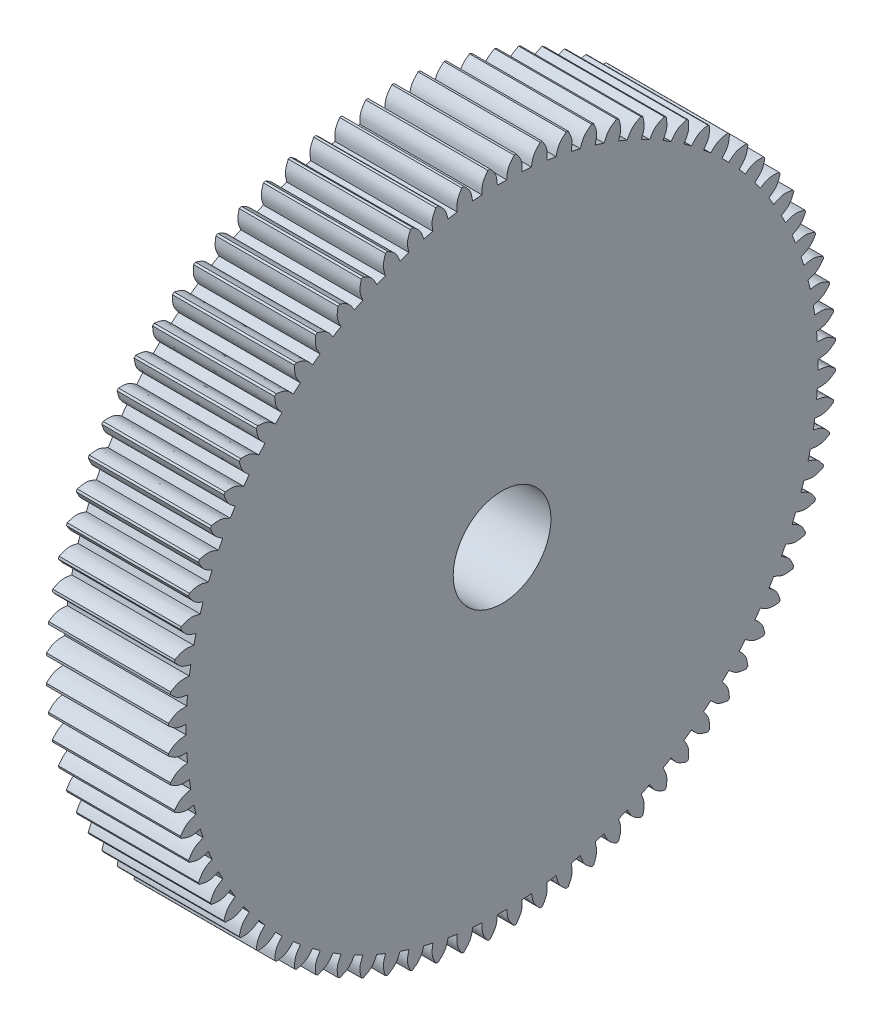
SolidWorks part; units mm, degrees
ref_plane "Front" through (0, 0, 0) normal (0, 0, 1) x (1, 0, 0)
ref_plane "Top" through (0, 0, 0) normal (0, 1, 0) x (1, 0, 0)
ref_plane "Right" through (0, 0, 0) normal (1, 0, 0) x (0, 0, -1)
sketch "Ritning 1" plane through (0, 0, 0) normal (0, 0, 1) x (1, 0, 0)
  line L0 (-7.5, -20.5) -> (7.5, -20.5) construction
  line L1 (-7.5, -14.5) -> (7.5, -14.5)
  line L2 (7.5, 20.5) -> (7.5, -14.5)
  line L3 (7.5, 20.5) -> (-7.5, 20.5)
  line L4 (-7.5, 20.5) -> (-7.5, -14.5)
  line L5 (-7.5, -14.5) -> (-7.5, -20.5) construction
  line L6 (-7.5, -20.5) -> (7.5, -20.5) construction
  dimension "D1" = 7.5
  dimension "D2" = 7.5
  dimension "D3" = 20.5
  dimension "D4" = 14.5
  dimension "D5" = 20.5
revolve "Kugghjulsämne" add sketch "Ritning 1" angle 360 about L0
sketch "Ritning 2" plane through (-7.5, 0, 0) normal (-1, 0, 0) x (0, 0, 1)
  line L0 (0, -20.5) -> (0, 20.5) construction
  line L1 (1.4725, 20.4735) -> (0, 21.946)
  line L2 (-1.4725, 20.4735) -> (0, 21.946)
  line L3 (0, -20.5) -> (5.3012, -20.5) construction
  arc A0 (0.5744, 18.2957) -> (-0.5744, 18.2957) centre (0, -20.5) ccw
  circle A1 centre (0, -20.5) radius 41 construction
  spline S0 degree 3 poles (1.4725, 20.4735) (1.2038, 20.1629) (0.6626, 19.5371) (0.604, 18.7115) (0.5744, 18.2957) knots 0 0 0 0 0.496456 1 1 1 1
  spline S1 degree 3 poles (-1.4725, 20.4735) (-1.2038, 20.1629) (-0.6626, 19.5371) (-0.604, 18.7115) (-0.5744, 18.2957) knots 0 0 0 0 0.496456 1 1 1 1
  dimension "D1" = 38.8
  dimension "D2" = 0.5744
  dimension "D3" = 0.7854
  dimension "D4" = 1.4725
  dimension "D5" = 39.9923
  dimension "D6" = 0.7854
  dimension "D7" = 40.9735
extrude "Kugglucka" cut sketch "Ritning 2" against normal up to surface (15 mm away) up to face at (7.5, -20.5, 41)
pattern_circular "CirPattern" count 80 over 360 about axis through (-7.5, -20.5, 0) along (-1, 0, 0) of "Kugglucka"
